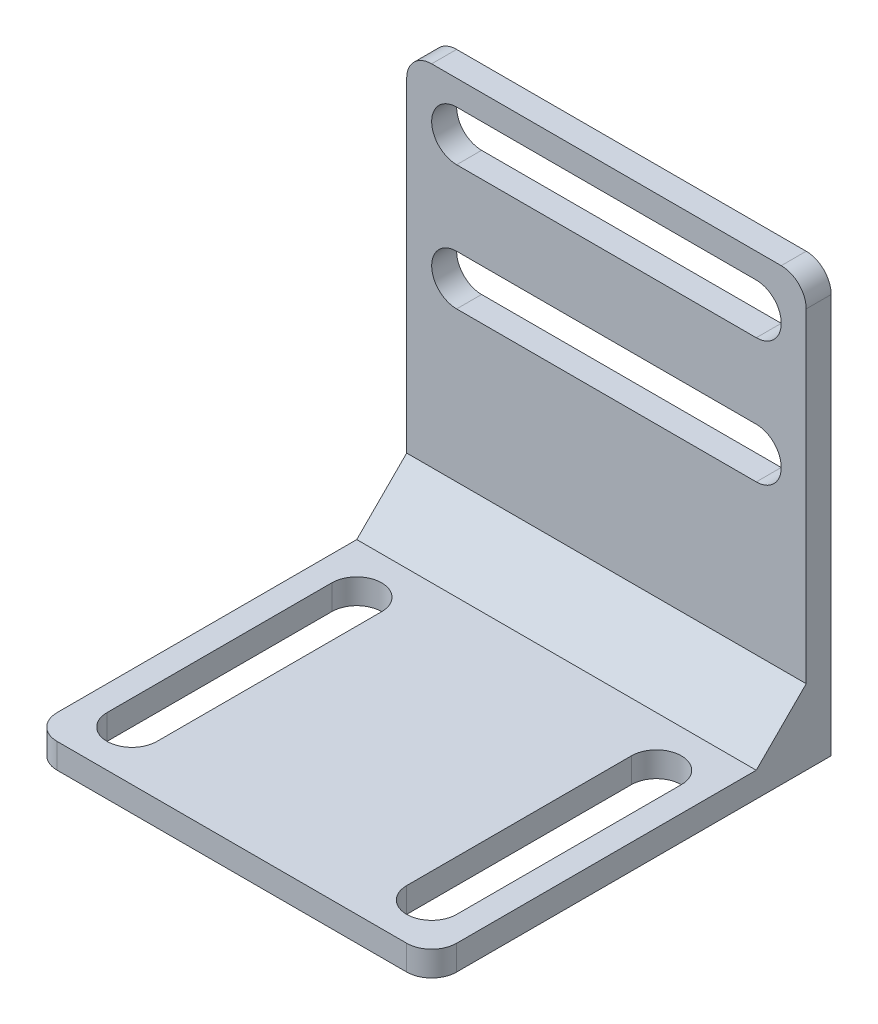
SolidWorks part; units mm, degrees
ref_plane "Front" through (0, 0, 0) normal (0, 0, 1) x (1, 0, 0)
ref_plane "Top" through (0, 0, 0) normal (0, 1, 0) x (1, 0, 0)
ref_plane "Right" through (0, 0, 0) normal (1, 0, 0) x (0, 0, -1)
sketch "Sketch1" plane through (0, 0, 0) normal (0, 1, 0) x (1, 0, 0)
  line L1 (-40, 40) -> (40, 40)
  line L2 (-40, 40) -> (-40, -40)
  line L3 (-40, -40) -> (40, -40)
  line L4 (40, 40) -> (40, -40)
  line L5 (-40, 40) -> (40, -40) construction
  line L6 (-40, -40) -> (40, 40) construction
  point P0 (0, 0)
  dimension "D1" = 80
extrude "Boss-Extrude1" add sketch "Sketch1" along normal blind 5
sketch "Sketch2" plane through (0, 5, 0) normal (0, 1, 0) x (1, 0, 0)
  line L0 (40, -40) -> (40, 40) construction
  line L1 (-40, 40) -> (40, 40)
  line L2 (-40, 40) -> (-40, 35)
  line L3 (-40, 35) -> (40, 35)
  line L4 (40, 40) -> (40, 35)
  dimension "D1" = 5
extrude "Boss-Extrude2" add sketch "Sketch2" along normal blind 80
sketch "Sketch4" plane through (40, 0, 0) normal (1, 0, 0) x (0, 0, -1)
  line L0 (25, 5) -> (35, 15)
  line L1 (-40, 5) -> (35, 5) construction
  line L2 (35, 85) -> (35, 5) construction
  dimension "D1" = 10
  dimension "D2" = 45
sketch "Sketch5" plane through (-40, 0, 0) normal (-1, 0, 0) x (0, 0, 1)
  line L0 (-25, 5) -> (-35, 15) construction
  line L1 (-25, 5) -> (-35, 15)
rib "Rib5" [suppressed] sketch "Sketch4" sketch "Sketch4" thickness 5 extrusion direction parallel to sketch draft on no parameters "D1"=5
rib "Rib6" [suppressed] sketch "Sketch5" sketch "Sketch5" thickness 5 extrusion direction parallel to sketch draft on no parameters "D1"=5
sketch "Sketch6" plane through (0, 0, -40) normal (0, 0, -1) x (-1, 0, 0)
  line L0 (-30, 75) -> (30, 75) construction
  line L1 (-30, 80) -> (30, 80)
  line L2 (-30, 70) -> (30, 70)
  line L3 (-30, 50) -> (30, 50) construction
  line L4 (-30, 55) -> (30, 55)
  line L5 (-30, 45) -> (30, 45)
  line L6 (-40, 85) -> (40, 85) construction
  arc A0 (-30, 80) -> (-30, 70) centre (-30, 75) ccw
  arc A1 (30, 70) -> (30, 80) centre (30, 75) ccw
  arc A2 (-30, 55) -> (-30, 45) centre (-30, 50) ccw
  arc A3 (30, 45) -> (30, 55) centre (30, 50) ccw
  point P2 (0, 75)
  point P7 (0, 50)
  point P17 (0, 85)
  dimension "D1" = 5
  dimension "D2" = 10
  dimension "D3" = 60
  dimension "D4" = 25
extrude "Cut-Extrude1" cut sketch "Sketch6" against normal through all
sketch "Sketch7" plane through (0, 5, 0) normal (0, 1, 0) x (1, 0, 0)
  line L0 (-30, -30) -> (-30, 15) construction
  line L1 (-35, -30) -> (-35, 15)
  line L2 (-25, -30) -> (-25, 15)
  line L3 (30, 15) -> (30, -30) construction
  line L4 (35, 15) -> (35, -30)
  line L5 (25, 15) -> (25, -30)
  line L9 (-40, -40) -> (40, -40) construction
  arc A0 (-35, -30) -> (-25, -30) centre (-30, -30) ccw
  arc A1 (-25, 15) -> (-35, 15) centre (-30, 15) ccw
  arc A2 (35, 15) -> (25, 15) centre (30, 15) ccw
  arc A3 (25, -30) -> (35, -30) centre (30, -30) ccw
  point P2 (-30, -7.5)
  point P7 (30, -7.5)
  dimension "D1" = 5
  dimension "D5" = 45
  dimension "D2" = 30
  dimension "D3" = 30
  dimension "D4" = 10
extrude "Cut-Extrude2" cut sketch "Sketch7" against normal through all
fillet "Fillet1" radius 5 2 edges at (-40, 2.5, 40) (40, 2.5, 40)
fillet "Fillet2" radius 5 2 edges at (-40, 85, -37.5) (40, 85, -37.5)
sketch "Sketch8" plane through (40, 0, 0) normal (1, 0, 0) x (0, 0, -1)
  line L0 (25, 5) -> (35, 15) construction
  line L1 (25, 5) -> (35, 15)
  line L2 (-35, 5) -> (35, 5) construction
  line L3 (35, 80) -> (35, 5) construction
  line L4 (-35, 5) -> (35, 5)
  line L5 (35, 80) -> (35, 5)
  line M3 (35, 80) -> (35, 5)
  line M4 (35, 5) -> (-35, 5)
extrude "Boss-Extrude3" add sketch "Sketch8" against normal up to surface (80 mm away) contours L1 M4 M3 region at (40, 8.3333, -31.6667) up to face at (-40, 28.3333, -13.3333)
equation "\"D3@Sketch7\"=\"D2@Sketch7\""
